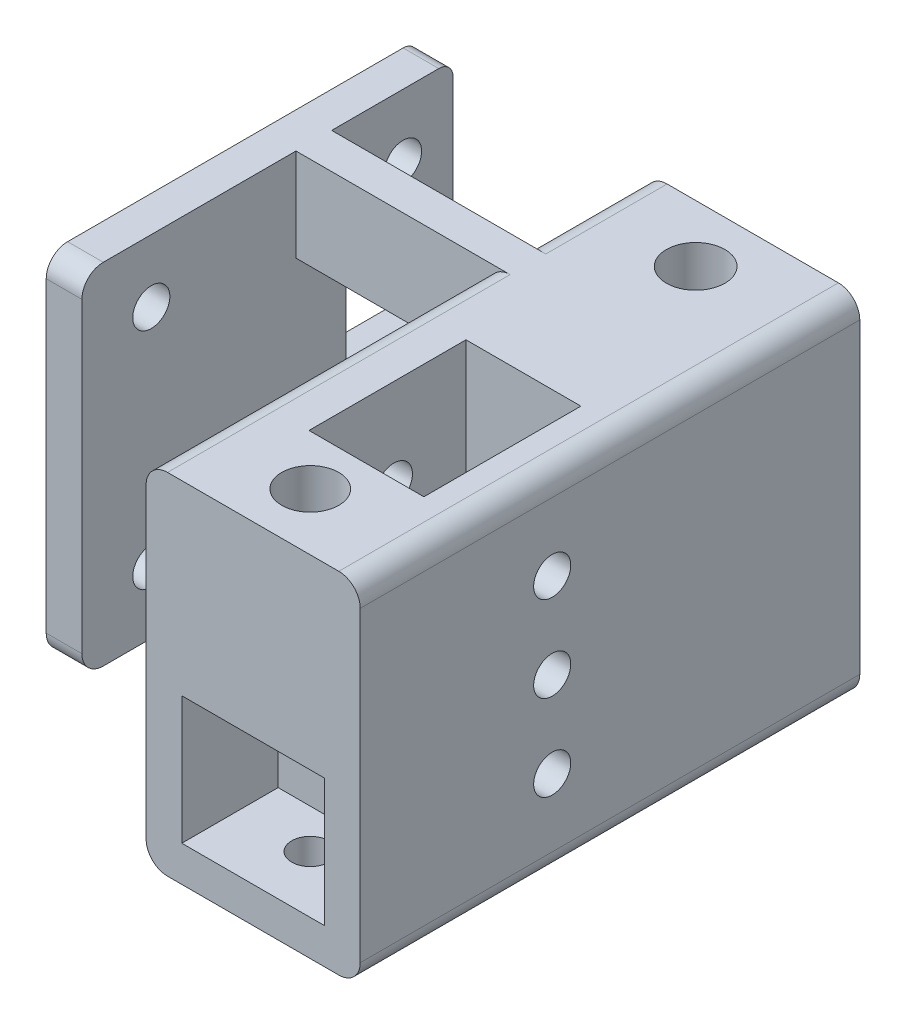
SolidWorks part; units mm, degrees
ref_plane "Front Plane" through (0, 0, 0) normal (0, 0, 1) x (1, 0, 0)
ref_plane "Top Plane" through (0, 0, 0) normal (0, 1, 0) x (1, 0, 0)
ref_plane "Right Plane" through (0, 0, 0) normal (1, 0, 0) x (0, 0, -1)
sketch "Sketch1" plane through (0, 0, 0) normal (0, 0, 1) x (1, 0, 0)
  circle A0 centre (0, 0) radius 11
  dimension "D1" = 22
extrude "Boss-Extrude1" add sketch "Sketch1" along normal blind 3
sketch "Sketch2" plane through (0, 0, 3) normal (0, 0, 1) x (1, 0, 0)
  circle A0 centre (0, 0) radius 5.25
  dimension "D1" = 10.5
extrude "Cut-Extrude1" cut sketch "Sketch2" against normal through all
sketch "Sketch3" plane through (0, 0, 3) normal (0, 0, 1) x (1, 0, 0)
  circle A0 centre (0, 8.5) radius 1.5
  circle A1 centre (-8.5, 0) radius 1.5
  circle A2 centre (0, -8.5) radius 1.5457
  circle A3 centre (8.5, 0) radius 1.5
  dimension "D1" = 3
  dimension "D2" = 3.0914
  dimension "D3" = 3
  dimension "D4" = 3
extrude "Cut-Extrude2" cut sketch "Sketch3" against normal through all
sketch "Sketch4" plane through (0, 0, 0) normal (0, 1, 0) x (1, 0, 0)
  line L1 (27.8591, -3) -> (0, -3)
  line L2 (27.8591, -3) -> (27.8591, -0.9879)
  line L3 (27.8591, -0.9879) -> (0, -0.9879)
  line L4 (0, -3) -> (0, -0.9879)
  dimension "D1" = 2.0121
extrude "Boss-Extrude3" add sketch "Sketch4" along normal mid plane 22
sketch "Sketch5" plane through (0, 0, 0.9879) normal (0, 0, -1) x (-1, 0, 0)
  circle A0 centre (0, 0) radius 5.25
extrude "Cut-Extrude3" cut sketch "Sketch5" against normal through all
sketch "Sketch6" plane through (0, 0, 0) normal (0, 0, -1) x (-1, 0, 0)
  line L0 (0, 10) -> (0, 7) construction
  line L1 (0, -6.9543) -> (0, -10.0457) construction
  circle A0 centre (-8.5, 0) radius 1.5
  circle A1 centre (0, 8.5) radius 1.5
  circle A2 centre (0, -8.5) radius 1.5457
extrude "Cut-Extrude4" cut sketch "Sketch6" against normal through all
sketch "Sketch7" plane through (0, 0, 0.9879) normal (0, 0, -1) x (-1, 0, 0)
  line L0 (-11, 0) -> (-24, 0)
  line L1 (-27.8591, -11) -> (0, -11) construction
  line L2 (-27.8591, 11) -> (-24, 11)
  line L3 (-27.8591, 11) -> (-27.8591, -11)
  line L4 (-27.8591, -11) -> (-24, -11)
  line L5 (-24, 11) -> (-24, -11)
  arc A0 (0, 11) -> (0, -11) centre (0, 0) ccw construction
  line M6 (-27.8591, -11) -> (0, -11)
  line M8 (0, 11) -> (-27.8591, 11)
  line M9 (-27.8591, 11) -> (-27.8591, -11)
  dimension "D1" = 13
extrude "Cut-Extrude5" cut sketch "Sketch7" against normal blind 10 contours L5 M8 M9 M6 region at (25.9295, 0, 0.9879)
sketch "Sketch10" plane through (0, 0, 3) normal (0, 0, 1) x (1, 0, 0)
  line L1 (0, 11) -> (24, 11)
  line L2 (0, 11) -> (0, -11)
  line L3 (0, -11) -> (24, -11)
  line L4 (24, 11) -> (24, -11)
  circle A0 centre (0, 0) radius 11
  circle M1 centre (8.5, 0) radius 1.5
  circle M2 centre (0, 8.5) radius 1.5
  circle M3 centre (0, -8.5) radius 1.5457
  circle M4 centre (0, 0) radius 5.25
  circle M5 centre (-8.5, 0) radius 1.5
  line M6 (0, -11) -> (24, -11)
  line M7 (24, -11) -> (24, 11)
  line M8 (24, 11) -> (0, 11)
  arc M9 (0, 11) -> (0, -11) centre (0, 0) ccw
extrude "Boss-Extrude5" add sketch "Sketch10" along normal blind 5 contours A0 M6 M7 M8 | L2 A0 M2 M4 M3 M1 | L2 M9 M3 M4 M2 M5 region at (5.4833, 0.014, 3) region at (16.1235, 0, 3) region at (-5.4833, 0.014, 3)
sketch "Sketch11" plane through (0, -11, 0) normal (0, -1, 0) x (1, 0, 0)
  line L0 (24, 0.9879) -> (0, 0.9879) construction
  line L1 (24, 8) -> (6, 8)
  line L2 (24, 8) -> (24, 0.9879)
  line L3 (24, 0.9879) -> (6, 0.9879)
  line L4 (6, 8) -> (6, 0.9879)
  dimension "D1" = 18
extrude "Boss-Extrude7" add sketch "Sketch11" along normal blind 13
sketch "Sketch13" plane through (0, 0, 0.9879) normal (0, 0, -1) x (-1, 0, 0)
  line L0 (-6, -11) -> (-34.4381, -11) construction
  line L1 (-24, 11) -> (-24, -24) construction
  line L2 (-24, -14.5) -> (-18, -14.5)
  line L3 (-24, -14.5) -> (-24, -22.5)
  line L4 (-24, -22.5) -> (-18, -22.5)
  line L5 (-18, -14.5) -> (-18, -22.5)
  dimension "D1" = 0
  dimension "D2" = 8
  dimension "D3" = 3.5
  dimension "D4" = 6
extrude "Boss-Extrude8" add sketch "Sketch13" along normal blind 10
sketch "Sketch14" plane through (0, 0, 0.9879) normal (0, 0, -1) x (-1, 0, 0)
  line L1 (-6, -24) -> (-24, -24)
  line L2 (-6, -24) -> (-6, -22.5)
  line L3 (-6, -22.5) -> (-24, -22.5)
  line L4 (-24, -24) -> (-24, -22.5)
extrude "Cut-Extrude6" cut sketch "Sketch14" against normal blind 10
sketch "Sketch15" plane through (0, 0, 8) normal (0, 0, 1) x (1, 0, 0)
  line L0 (6, -11) -> (35.8842, -11) construction
  line L1 (24, -22.5) -> (16, -22.5)
  line L2 (24, -22.5) -> (24, -14.5)
  line L3 (24, -14.5) -> (16, -14.5)
  line L4 (16, -22.5) -> (16, -14.5)
  dimension "D1" = 3.5
  dimension "D2" = 8
extrude "Boss-Extrude9" add sketch "Sketch15" along normal blind 30
sketch "Sketch16" plane through (0, 0, 0.9879) normal (0, 0, -1) x (-1, 0, 0)
  line L0 (-24, -14.5) -> (5.1357, -14.5) construction
  line L2 (-18, -22.5) -> (-16, -22.5)
  line L3 (-18, -22.5) -> (-18, -14.5)
  line L4 (-18, -14.5) -> (-16, -14.5)
  line L5 (-16, -22.5) -> (-16, -14.5)
  dimension "D1" = 2
extrude "Boss-Extrude10" add sketch "Sketch16" along normal blind 10
sketch "Sketch18" plane through (24, 0, 0) normal (1, 0, 0) x (0, 0, -1)
  line L1 (-38, -14.5) -> (9.0121, -14.5)
  line L2 (-38, -14.5) -> (-38, -11)
  line L3 (-38, -11) -> (9.0121, -11)
  line L4 (9.0121, -14.5) -> (9.0121, -11)
  dimension "D1" = 3.5
extrude "Boss-Extrude11" add sketch "Sketch18" against normal blind 8
sketch "Sketch19" plane through (24, 0, 0) normal (1, 0, 0) x (0, 0, -1)
  line L1 (-38, -11) -> (9.0121, -11)
  line L2 (-38, -11) -> (-38, -6)
  line L3 (-38, -6) -> (9.0121, -6)
  line L4 (9.0121, -11) -> (9.0121, -6)
  dimension "D1" = 5
extrude "Boss-Extrude12" add sketch "Sketch19" against normal blind 8
sketch "Sketch20" plane through (24, 0, 0) normal (1, 0, 0) x (0, 0, -1)
  line L0 (9.0121, -6) -> (9.0121, -11) construction
  line L1 (9.0121, -6) -> (9.0121, -22.5) construction
  line L2 (9.0121, -11) -> (-47.1773, -11) construction
  line L3 (9.0121, -11) -> (9.0121, -14.5) construction
  line L4 (9.0121, -14.5) -> (-46.6015, -14.5) construction
  line L5 (9.0121, -14.5) -> (9.0121, -19.5) construction
  line L6 (9.0121, -17) -> (-43.5925, -17) construction
  circle A0 centre (2.7978, -17) radius 2.75
  dimension "D4" = 5.5
  dimension "D1" = 5
  dimension "D2" = 3.5
  dimension "D3" = 5
extrude "Cut-Extrude7" cut sketch "Sketch20" against normal blind 8
sketch "Sketch21" plane through (24, 0, 0) normal (1, 0, 0) x (0, 0, -1)
  line L1 (-38, -22.5) -> (-8, -22.5)
  line L2 (-38, -22.5) -> (-38, -6)
  line L3 (-38, -6) -> (-8, -6)
  line L4 (-8, -22.5) -> (-8, -6)
extrude "Cut-Extrude8" cut sketch "Sketch21" against normal blind 8
sketch "Sketch22" plane through (0, -22.5, 0) normal (0, -1, 0) x (1, 0, 0)
  line L0 (6, 8) -> (24, 8)
  line L1 (24, 8) -> (24, -9.0121)
  line L2 (24, -9.0121) -> (16, -9.0121)
  line L3 (16, -9.0121) -> (16, 0.9879)
  line L4 (16, 0.9879) -> (6, 0.9879)
  line L5 (6, 0.9879) -> (6, 8)
extrude "Boss-Extrude13" add sketch "Sketch22" along normal blind 2
fillet "Fillet4" radius 2 2 edges at (20, -6, -9.0121) (20, -24.5, -9.0121)
sketch "Sketch24" plane through (0, 11, 0) normal (0, 1, 0) x (1, 0, 0)
  line L0 (24, -8) -> (0, -8) construction
  line L1 (24, -0.9879) -> (6, -0.9879)
  line L2 (24, -0.9879) -> (24, -8)
  line L3 (24, -8) -> (6, -8)
  line L4 (6, -0.9879) -> (6, -8)
  dimension "D1" = 18
extrude "Boss-Extrude14" add sketch "Sketch24" along normal blind 13.5
sketch "Sketch25" plane through (24, 0, 0) normal (1, 0, 0) x (0, 0, -1)
  line L1 (-0.9879, 24.5) -> (9.2401, 24.5)
  line L2 (-0.9879, 24.5) -> (-0.9879, 6)
  line L3 (-0.9879, 6) -> (9.2401, 6)
  line L4 (9.2401, 24.5) -> (9.2401, 6)
  dimension "D1" = 18.5
extrude "Boss-Extrude15" add sketch "Sketch25" against normal blind 8
sketch "Sketch26" plane through (24, 0, 0) normal (1, 0, 0) x (0, 0, -1)
  line L0 (9.2401, 6) -> (9.2401, 11) construction
  line L1 (9.2401, 6) -> (9.2401, 24.5) construction
  line L2 (9.2401, 11) -> (-25.444, 11) construction
  line L3 (9.2401, 11) -> (9.2401, 14.5) construction
  line L4 (9.2401, 14.5) -> (-21.9918, 14.5) construction
  line L5 (9.2401, 14.5) -> (9.2401, 19.5) construction
  line L6 (2.7978, -17) -> (2.7978, 39.4291) construction
  circle A0 centre (2.7978, 17) radius 2.6
  dimension "D4" = 5.2
  dimension "D1" = 5
  dimension "D2" = 3.5
  dimension "D3" = 5
extrude "Cut-Extrude9" cut sketch "Sketch26" against normal blind 8
fillet "Fillet6" radius 2 2 edges at (20, 24.5, -9.2401) (20, 6, -9.2401)
sketch "Sketch27" plane through (24, 0, 0) normal (1, 0, 0) x (0, 0, -1)
  line L1 (-1.9691, 21.4381) -> (6.5233, 21.4381)
  line L2 (-1.9691, 21.4381) -> (-1.9691, 12.6005)
  line L3 (-1.9691, 12.6005) -> (6.5233, 12.6005)
  line L4 (6.5233, 21.4381) -> (6.5233, 12.6005)
extrude "Boss-Extrude16" add sketch "Sketch27" against normal blind 8
sketch "Sketch28" plane through (24, 0, 0) normal (1, 0, 0) x (0, 0, -1)
  line L0 (-0.9879, -6) -> (-0.9879, -11) construction
  line L2 (-2.5214, -12.8767) -> (6.8685, -12.8767)
  line L3 (-2.5214, -12.8767) -> (-2.5214, -20.1263)
  line L4 (-2.5214, -20.1263) -> (6.8685, -20.1263)
  line L5 (6.8685, -12.8767) -> (6.8685, -20.1263)
extrude "Boss-Extrude17" add sketch "Sketch28" against normal blind 8
sketch "Sketch30" plane through (0, 0, -9.2401) normal (0, 0, -1) x (-1, 0, 0)
  line L1 (-24, 22.5) -> (-16, 22.5)
  line L2 (-24, 22.5) -> (-24, 24.5)
  line L3 (-24, 24.5) -> (-16, 24.5)
  line L4 (-16, 22.5) -> (-16, 24.5)
  line L5 (-24, 8) -> (-16, 8)
  line L6 (-24, 8) -> (-24, 6)
  line L7 (-24, 6) -> (-16, 6)
  line L8 (-16, 8) -> (-16, 6)
extrude "Boss-Extrude19" add sketch "Sketch30" against normal blind 8
sketch "Sketch31" plane through (0, 0, -9.0121) normal (0, 0, -1) x (-1, 0, 0)
  line L1 (-24, -8) -> (-16, -8)
  line L2 (-24, -8) -> (-24, -6)
  line L3 (-24, -6) -> (-16, -6)
  line L4 (-16, -8) -> (-16, -6)
  line L5 (-24, -22.5) -> (-16, -22.5)
  line L6 (-24, -22.5) -> (-24, -24.5)
  line L7 (-24, -24.5) -> (-16, -24.5)
  line L8 (-16, -22.5) -> (-16, -24.5)
extrude "Boss-Extrude20" add sketch "Sketch31" against normal blind 8
sketch "Sketch32" plane through (0, 0, -9.2401) normal (0, 0, -1) x (-1, 0, 0)
  line L1 (-24, 24.5) -> (-16, 24.5)
  line L2 (-24, 24.5) -> (-24, 6)
  line L3 (-24, 6) -> (-16, 6)
  line L4 (-16, 24.5) -> (-16, 6)
extrude "Boss-Extrude22" add sketch "Sketch32" along normal blind 5
sketch "Sketch33" plane through (0, 0, -9.0121) normal (0, 0, -1) x (-1, 0, 0)
  line L1 (-24, -6) -> (-16, -6)
  line L2 (-24, -6) -> (-24, -24.5)
  line L3 (-24, -24.5) -> (-16, -24.5)
  line L4 (-16, -6) -> (-16, -24.5)
extrude "Boss-Extrude23" add sketch "Sketch33" along normal blind 5
sketch "Sketch34" plane through (24, 0, 0) normal (1, 0, 0) x (0, 0, -1)
  line L0 (-0.9879, -11) -> (-0.9879, 11) construction
  line L1 (-0.9879, -6) -> (-0.9879, -11) construction
  line L3 (-0.9879, -11) -> (-0.9879, -14.2) construction
  line L5 (-0.9879, -14.2) -> (-0.9879, -19.2) construction
  line L9 (6.5121, -6) -> (6.5121, -24.5) construction
  line L10 (14.0121, -6) -> (-0.9879, -6) construction
  line L11 (14.0121, -24.5) -> (-8, -24.5) construction
  circle A0 centre (6.0121, 16.7) radius 2.6
  dimension "D8" = 5.2
  dimension "D1" = 7
  dimension "D2" = 5
  dimension "D4" = 3.2
  dimension "D6" = 5
extrude "Cut-Extrude11" cut sketch "Sketch34" against normal through all
sketch "Sketch35" plane through (24, 0, 0) normal (1, 0, 0) x (0, 0, -1)
  line L0 (14.0121, -6) -> (-0.9879, -6) construction
  circle A0 centre (6.0121, -16.7) radius 2.6
  dimension "D1" = 5.2
  dimension "D2" = 10.7
extrude "Cut-Extrude12" cut sketch "Sketch35" against normal through all
sketch "Sketch36" plane through (0, -24.5, 0) normal (0, -1, 0) x (1, 0, 0)
  line L1 (16, -14.2401) -> (24, -14.2401)
  line L2 (16, -14.2401) -> (16, -14.0121)
  line L3 (16, -14.0121) -> (24, -14.0121)
  line L4 (24, -14.2401) -> (24, -14.0121)
extrude "Cut-Extrude13" cut sketch "Sketch36" against normal through all
sketch "Sketch37" plane through (0, 0, -14.0121) normal (0, 0, -1) x (-1, 0, 0)
  line L0 (-24, -24.5) -> (-16, -24.5) construction
  line L1 (-16, -6) -> (-19, -6)
  line L2 (-16, -6) -> (-16, -24.5)
  line L3 (-16, -24.5) -> (-19, -24.5)
  line L4 (-19, -6) -> (-19, -24.5)
  dimension "D1" = 3
extrude "Cut-Extrude14" cut sketch "Sketch37" against normal blind 15
sketch "Sketch38" plane through (0, 0, -14.0121) normal (0, 0, -1) x (-1, 0, 0)
  line L0 (-24, 6) -> (-16, 6) construction
  line L1 (-16, 24.5) -> (-19, 24.5)
  line L2 (-16, 24.5) -> (-16, 6)
  line L3 (-16, 6) -> (-19, 6)
  line L4 (-19, 24.5) -> (-19, 6)
  dimension "D1" = 3
extrude "Cut-Extrude15" cut sketch "Sketch38" against normal blind 15
fillet "Fillet9" radius 2 4 edges at (21.5, -24.5, -14.0121) (21.5, -6, -14.0121) (21.5, 24.5, -14.0121) (21.5, 6, -14.0121)
sketch "Sketch39" plane through (24, 0, 0) normal (1, 0, 0) x (0, 0, -1)
  line L1 (2.5573, 21.5762) -> (10.9806, 21.5762)
  line L2 (2.5573, 21.5762) -> (2.5573, 11.841)
  line L3 (2.5573, 11.841) -> (10.9806, 11.841)
  line L4 (10.9806, 21.5762) -> (10.9806, 11.841)
  line L5 (1.7978, -12.6696) -> (10.4283, -12.6696)
  line L6 (1.7978, -12.6696) -> (1.7978, -21.0239)
  line L7 (1.7978, -21.0239) -> (10.4283, -21.0239)
  line L8 (10.4283, -12.6696) -> (10.4283, -21.0239)
extrude "Boss-Extrude24" add sketch "Sketch39" against normal blind 8
sketch "Sketch40" plane through (24, 0, 0) normal (1, 0, 0) x (0, 0, -1)
  line L0 (-0.9879, 6) -> (12.0121, 6) construction
  line L1 (-8, -24.5) -> (-8, 24.5) construction
  circle A0 centre (7, 15.7) radius 2.6
  dimension "D2" = 15
  dimension "D3" = 5.2
  dimension "D1" = 9.7
extrude "Cut-Extrude16" cut sketch "Sketch40" against normal blind 8
sketch "Sketch41" plane through (0, 0, -10.9806) normal (0, 0, -1) x (-1, 0, 0)
  line L1 (-16, 21.5762) -> (-19, 21.5762)
  line L2 (-16, 21.5762) -> (-16, 11.841)
  line L3 (-16, 11.841) -> (-19, 11.841)
  line L4 (-19, 21.5762) -> (-19, 11.841)
extrude "Cut-Extrude18" cut sketch "Sketch41" against normal blind 9
sketch "Sketch42" plane through (0, 0, -10.4283) normal (0, 0, -1) x (-1, 0, 0)
  line L1 (-19, -12.6696) -> (-16, -12.6696)
  line L2 (-19, -12.6696) -> (-19, -21.0239)
  line L3 (-19, -21.0239) -> (-16, -21.0239)
  line L4 (-16, -12.6696) -> (-16, -21.0239)
extrude "Cut-Extrude19" cut sketch "Sketch42" against normal blind 9
sketch "Sketch43" plane through (24, 0, 0) normal (1, 0, 0) x (0, 0, -1)
  line L0 (12.0121, -6) -> (-0.9879, -6) construction
  line L1 (-8, -24.5) -> (-8, 24.5) construction
  circle A0 centre (7, -15.7) radius 2.6
  dimension "D1" = 5.2
  dimension "D3" = 15
  dimension "D2" = 9.7
extrude "Cut-Extrude20" cut sketch "Sketch43" against normal blind 9
sketch "Sketch48" plane through (0, 0, 8) normal (0, 0, 1) x (1, 0, 0)
  line L1 (24, -24.5) -> (46, -24.5)
  line L2 (24, -24.5) -> (24, -11.5)
  line L3 (24, -11.5) -> (46, -11.5)
  line L4 (46, -24.5) -> (46, -11.5)
  dimension "D1" = 13
  dimension "D2" = 22
extrude "Boss-Extrude26" add sketch "Sketch48" against normal blind 5
sketch "Sketch49" plane through (0, 0, 8) normal (0, 0, 1) x (1, 0, 0)
  line L1 (24, 24.5) -> (46, 24.5)
  line L2 (24, 24.5) -> (24, 11.5)
  line L3 (24, 11.5) -> (46, 11.5)
  line L4 (46, 24.5) -> (46, 11.5)
  dimension "D1" = 22
  dimension "D2" = 13
extrude "Boss-Extrude27" add sketch "Sketch49" against normal blind 5
sketch "Sketch50" plane through (46, 0, 0) normal (1, 0, 0) x (0, 0, -1)
  line L1 (-8, 24.5) -> (-3, 24.5)
  line L2 (-8, 24.5) -> (-8, -24.5)
  line L3 (-8, -24.5) -> (-3, -24.5)
  line L4 (-3, 24.5) -> (-3, -24.5)
extrude "Boss-Extrude28" add sketch "Sketch50" along normal blind 15
sketch "Sketch51" plane through (0, 0, 8) normal (0, 0, 1) x (1, 0, 0)
  line L0 (61, 24.5) -> (61, -24.5) construction
  line L1 (6, 24.5) -> (61, 24.5)
  line L2 (6, 24.5) -> (6, 19.5)
  line L3 (6, 19.5) -> (61, 19.5)
  line L4 (61, 24.5) -> (61, 19.5)
  dimension "D1" = 5
extrude "Boss-Extrude29" add sketch "Sketch51" along normal blind 42.8
sketch "Sketch52" plane through (0, 19.5, 0) normal (0, -1, 0) x (1, 0, 0)
  line L1 (6, 50.8) -> (61, 50.8)
  line L2 (6, 50.8) -> (6, 55.8)
  line L3 (6, 55.8) -> (61, 55.8)
  line L4 (61, 50.8) -> (61, 55.8)
  dimension "D1" = 5
extrude "Boss-Extrude30" add sketch "Sketch52" against normal blind 47.8
sketch "Sketch53" plane through (0, 0, 55.8) normal (0, 0, 1) x (1, 0, 0)
  line L1 (6, 67.3) -> (61, 67.3)
  line L2 (6, 67.3) -> (6, 72.3)
  line L3 (6, 72.3) -> (61, 72.3)
  line L4 (61, 67.3) -> (61, 72.3)
  dimension "D1" = 5
extrude "Boss-Extrude31" add sketch "Sketch53" against normal blind 47.8
sketch "Sketch55" plane through (0, 72.3, 0) normal (0, 1, 0) x (1, 0, 0)
  line L0 (61, -55.8) -> (6, -55.8) construction
  line L1 (61, -8) -> (46, -8)
  line L2 (61, -8) -> (61, -55.8)
  line L3 (61, -55.8) -> (46, -55.8)
  line L4 (46, -8) -> (46, -55.8)
  dimension "D1" = 15
extrude "Cut-Extrude21" cut sketch "Sketch55" against normal through all
sketch "Sketch57" plane through (46, 0, 0) normal (1, 0, 0) x (0, 0, -1)
  line L1 (-8, 72.3) -> (-55.8, 72.3)
  line L2 (-8, 72.3) -> (-8, 19.5)
  line L3 (-8, 19.5) -> (-55.8, 19.5)
  line L4 (-55.8, 72.3) -> (-55.8, 19.5)
extrude "Boss-Extrude32" add sketch "Sketch57" along normal blind 5
sketch "Sketch58" plane through (51, 0, 0) normal (1, 0, 0) x (0, 0, -1)
  circle A0 centre (-29.4, 45.9) radius 11.5
  dimension "D1" = 23
extrude "Cut-Extrude25" cut sketch "Sketch58" against normal through all
sketch "Sketch61" plane through (0, 72.3, 0) normal (0, 1, 0) x (1, 0, 0)
  line L0 (51, -8) -> (6, -8) construction
  line L1 (16, -45.8) -> (41, -45.8)
  line L2 (16, -45.8) -> (16, -18)
  line L3 (16, -18) -> (41, -18)
  line L4 (41, -45.8) -> (41, -18)
  line L5 (16, -45.8) -> (41, -18) construction
  line L6 (16, -18) -> (41, -45.8) construction
  line L7 (51, -55.8) -> (6, -55.8) construction
  line L8 (6, -8) -> (6, -55.8) construction
  line L9 (51, -8) -> (51, -55.8) construction
  point P0 (28.5, -31.9)
  dimension "D1" = 10
  dimension "D2" = 10
  dimension "D3" = 10
  dimension "D4" = 10
extrude "Cut-Extrude26" cut sketch "Sketch61" against normal through all
sketch "Sketch62" plane through (46, 0, 0) normal (-1, 0, 0) x (0, 0, 1)
  line L0 (50.8, 24.5) -> (8, 24.5) construction
  line L1 (50.8, 24.5) -> (50.8, 67.3) construction
  circle A0 centre (46.3, 29) radius 1.75
  dimension "D1" = 3.5
  dimension "D3" = 4.5
  dimension "D2" = 4.5
extrude "Cut-Extrude28" cut sketch "Sketch62" against normal through all
sketch "Sketch63" plane through (46, 0, 0) normal (-1, 0, 0) x (0, 0, 1)
  line L0 (8, 24.5) -> (8, 67.3) construction
  line L1 (50.8, 24.5) -> (8, 24.5) construction
  circle A0 centre (12.5, 29) radius 1.75
  dimension "D1" = 3.5
  dimension "D2" = 4.5
  dimension "D3" = 4.5
extrude "Cut-Extrude29" cut sketch "Sketch63" against normal through all
sketch "Sketch64" plane through (46, 0, 0) normal (-1, 0, 0) x (0, 0, 1)
  line L0 (50.8, 67.3) -> (8, 67.3) construction
  line L1 (50.8, 67.3) -> (50.8, 24.5) construction
  circle A0 centre (46.3, 62.8) radius 1.75
  dimension "D1" = 3.5
  dimension "D2" = 4.5
  dimension "D3" = 4.5
extrude "Cut-Extrude30" cut sketch "Sketch64" against normal through all
sketch "Sketch65" plane through (46, 0, 0) normal (-1, 0, 0) x (0, 0, 1)
  line L0 (8, 24.5) -> (8, 67.3) construction
  line L1 (50.8, 67.3) -> (8, 67.3) construction
  circle A0 centre (12.5, 62.8) radius 1.75
  dimension "D1" = 4.5
  dimension "D2" = 3.5
  dimension "D3" = 4.5
extrude "Cut-Extrude31" cut sketch "Sketch65" against normal through all
sketch "Sketch67" plane through (61, 0, 0) normal (1, 0, 0) x (0, 0, -1)
  line L1 (-8, 24.5) -> (-3, 24.5)
  line L2 (-8, 24.5) -> (-8, -24.5)
  line L3 (-8, -24.5) -> (-3, -24.5)
  line L4 (-3, 24.5) -> (-3, -24.5)
extrude "Boss-Extrude33" add sketch "Sketch67" along normal blind 5
sketch "Sketch68" plane through (0, -24.5, 0) normal (0, -1, 0) x (1, 0, 0)
  line L1 (66, 3) -> (51, 3)
  line L2 (66, 3) -> (66, -14.0121)
  line L3 (66, -14.0121) -> (51, -14.0121)
  line L4 (51, 3) -> (51, -14.0121)
  line L5 (66, 8) -> (51, 8)
  line L6 (66, 8) -> (66, 55.8)
  line L7 (66, 55.8) -> (51, 55.8)
  line L8 (51, 8) -> (51, 55.8)
extrude "Boss-Extrude34" add sketch "Sketch68" against normal blind 15
sketch "Sketch69" plane through (66, 0, 0) normal (1, 0, 0) x (0, 0, -1)
  line L0 (-55.8, -9.5) -> (-8, -9.5)
  line L1 (-8, -9.5) -> (-8, 24.5)
  line L2 (-8, 24.5) -> (-3, 24.5)
  line L3 (-3, 24.5) -> (-3, -9.5)
  line L4 (-3, -9.5) -> (14.0121, -9.5)
  line L5 (14.0121, -9.5) -> (14.0121, -24.5)
  line L6 (14.0121, -24.5) -> (-55.8, -24.5)
  line L7 (-55.8, -24.5) -> (-55.8, -9.5)
extrude "Boss-Extrude36" add sketch "Sketch69" along normal blind 15
sketch "Sketch70" plane through (0, -24.5, 0) normal (0, -1, 0) x (1, 0, 0)
  line L0 (81, 55.8) -> (51, 55.8) construction
  line L1 (51, -14.0121) -> (81, -14.0121) construction
  circle A0 centre (66, 47.8) radius 4.1
  circle A1 centre (66, -6.0121) radius 4.1
  dimension "D1" = 8
  dimension "D2" = 8.2
  dimension "D3" = 8.2
  dimension "D4" = 8
extrude "Cut-Extrude32" cut sketch "Sketch70" against normal blind 10
sketch "Sketch72" plane through (0, -24.5, 0) normal (0, -1, 0) x (1, 0, 0)
  line L1 (57, 40) -> (75, 40)
  line L2 (57, 40) -> (57, 18)
  line L3 (57, 18) -> (75, 18)
  line L4 (75, 40) -> (75, 18)
  line L5 (6, 8) -> (51, 8) construction
  line L6 (51, 55.8) -> (51, 8) construction
  line L9 (81, 55.8) -> (81, -14.0121) construction
  dimension "D1" = 6
  dimension "D2" = 10
  dimension "D3" = 22
  dimension "D4" = 6
extrude "Cut-Extrude33" cut sketch "Sketch72" against normal through all
fillet "Fillet10" radius 4 1 edges at (81, 24.5, 5.5)
fillet "Fillet12" radius 4 1 edges at (6, -24.5, 4.494)
fillet "Fillet13" radius 4 9 edges at (51, -17, -14.0121) (81, -9.5, -5.506) (81, -17, -14.0121) (81, -24.5, 20.894) (81, -9.5, 31.9) (51, -9.5, 31.9) (51, -9.5, -5.506) (51, -24.5, -5.506) (51, -24.5, 31.9)
sketch "Sketch77" plane through (0, 0, 0.9879) normal (0, 0, -1) x (-1, 0, 0)
  line L1 (-19, 24.5) -> (17.4446, 24.5)
  line L2 (-19, 24.5) -> (-19, -26.3623)
  line L3 (-19, -26.3623) -> (17.4446, -26.3623)
  line L4 (17.4446, 24.5) -> (17.4446, -26.3623)
extrude "Cut-Extrude38" cut sketch "Sketch77" against normal through all
sketch "Sketch78" plane through (0, 0, 8) normal (0, 0, -1) x (-1, 0, 0)
  line L1 (-51, 72.3) -> (-6, 72.3)
  line L2 (-51, 72.3) -> (-51, 24.5)
  line L3 (-51, 24.5) -> (-6, 24.5)
  line L4 (-6, 72.3) -> (-6, 24.5)
extrude "Cut-Extrude39" cut sketch "Sketch78" against normal through all
sketch "Sketch79" plane through (0, -24.5, 0) normal (0, -1, 0) x (1, 0, 0)
  line L1 (51, 3) -> (82.4311, 3)
  line L2 (51, 3) -> (51, -15.5183)
  line L3 (51, -15.5183) -> (82.4311, -15.5183)
  line L4 (82.4311, 3) -> (82.4311, -15.5183)
extrude "Cut-Extrude40" cut sketch "Sketch79" against normal through all
sketch "Sketch80" plane through (0, 24.5, 0) normal (0, 1, 0) x (1, 0, 0)
  line L0 (19, -55.8) -> (19, -45.8) construction
  line L1 (81, -8) -> (19, -8)
  line L2 (81, -8) -> (81, -55.8)
  line L3 (81, -55.8) -> (19, -55.8)
  line L4 (19, -8) -> (19, -55.8)
  line L5 (51, -55.8) -> (19, -55.8) construction
extrude "Cut-Extrude41" cut sketch "Sketch80" against normal through all
sketch "Sketch81" plane through (0, 0, 0) normal (0, 0, -1) x (-1, 0, 0)
  circle A0 centre (0, 0) radius 11
extrude "Cut-Extrude42" cut sketch "Sketch81" against normal through all
sketch "Sketch85" plane through (0, 0, 3) normal (0, 0, -1) x (-1, 0, 0)
  line L0 (-24, -24.5) -> (-77, -24.5) construction
  line L1 (-81, 24.5) -> (-51, 24.5)
  line L2 (-81, 24.5) -> (-81, -24.5)
  line L3 (-81, -24.5) -> (-51, -24.5)
  line L4 (-51, 24.5) -> (-51, -24.5)
  dimension "D1" = 30
extrude "Boss-Extrude37" add sketch "Sketch85" along normal blind 17
sketch "Sketch86" plane through (0, 0, -14) normal (0, 0, -1) x (-1, 0, 0)
  line L1 (-81, 24.5) -> (-51, 24.5)
  line L2 (-81, 24.5) -> (-81, -24.5)
  line L3 (-81, -24.5) -> (-51, -24.5)
  line L4 (-51, 24.5) -> (-51, -24.5)
extrude "Boss-Extrude39" add sketch "Sketch86" against normal blind 70
sketch "Sketch87" plane through (0, 24.5, 0) normal (0, 1, 0) x (1, 0, 0)
  line L0 (51, 14) -> (81, 14) construction
  line L1 (51, -56) -> (81, -56) construction
  line L3 (58.8194, -19) -> (74.9193, -19)
  line L4 (58.8194, -19) -> (58.8194, -41)
  line L5 (58.8194, -41) -> (74.9193, -41)
  line L6 (74.9193, -19) -> (74.9193, -41)
  circle A0 centre (66, 6) radius 4.1
  circle A1 centre (66, -48) radius 4
  dimension "D1" = 8.2
  dimension "D3" = 8
  dimension "D2" = 8
  dimension "D4" = 8
  dimension "D5" = 15
  dimension "D6" = 22
extrude "Cut-Extrude43" cut sketch "Sketch87" against normal blind 70
fillet "Fillet17" radius 3 5 edges at (51, -24.5, 32) (81, -24.5, 21) (81, 24.5, 21) (51, 24.5, 32) (51, 24.5, -5.5)
sketch "Sketch89" plane through (0, 0, 8) normal (0, 0, 1) x (1, 0, 0)
  line L1 (19, 24.5) -> (24, 24.5)
  line L2 (19, 24.5) -> (19, -24.5)
  line L3 (19, -24.5) -> (24, -24.5)
  line L4 (24, 24.5) -> (24, -24.5)
extrude "Boss-Extrude40" add sketch "Sketch89" along normal blind 30
sketch "Sketch92" plane through (19, 0, 0) normal (-1, 0, 0) x (0, 0, 1)
  circle A0 centre (28.274, 15.7) radius 2.6
  circle A1 centre (28.274, -15.7) radius 2.6
  dimension "D1" = 5.2
  dimension "D2" = 5.2
extrude "Cut-Extrude44" cut sketch "Sketch92" against normal blind 10
fillet "Fillet18" radius 3 2 edges at (21.5, -24.5, 38) (21.5, 24.5, 38)
sketch "Sketch93" plane through (0, 0, -14) normal (0, 0, -1) x (-1, 0, 0)
  line L0 (-81, 21.5) -> (-81, -21.5) construction
  line L1 (-76, -19.5) -> (-56, -19.5)
  line L2 (-76, -19.5) -> (-76, -1.5535)
  line L3 (-76, -1.5535) -> (-56, -1.5535)
  line L4 (-56, -19.5) -> (-56, -1.5535)
  line L5 (-51, -24.5) -> (-51, 21.5) construction
  line L6 (-78, -24.5) -> (-51, -24.5) construction
  dimension "D1" = 5
  dimension "D2" = 5
  dimension "D3" = 5
extrude "Cut-Extrude45" cut sketch "Sketch93" against normal blind 17.8
sketch "Sketch98" plane through (81, 0, 0) normal (1, 0, 0) x (0, 0, -1)
  line L0 (14, 21.5) -> (14, -21.5) construction
  circle A0 centre (-29.1, 0) radius 2.6
  dimension "D1" = 5.2
  dimension "D2" = 43.1
extrude "Cut-Extrude46" cut sketch "Sketch98" against normal blind 37.8
sketch "Sketch99" plane through (81, 0, 0) normal (1, 0, 0) x (0, 0, -1)
  circle A0 centre (-29.1, 12) radius 2.6
  circle A1 centre (-29.1, 0) radius 2.6 construction
  dimension "D1" = 5.2
  dimension "D2" = 12
extrude "Cut-Extrude48" cut sketch "Sketch99" against normal blind 37.8
sketch "Sketch100" plane through (81, 0, 0) normal (1, 0, 0) x (0, 0, -1)
  circle A0 centre (-29.1, -12) radius 2.6
  circle A1 centre (-29.1, 0) radius 2.6 construction
  dimension "D1" = 5.2
  dimension "D2" = 12
extrude "Cut-Extrude49" cut sketch "Sketch100" against normal blind 37.8
sketch "Sketch102" plane through (0, 0, 56) normal (0, 0, 1) x (1, 0, 0)
  line L0 (78, -24.5) -> (54, -24.5) construction
  line L1 (56, -1.6) -> (76, -1.6)
  line L2 (56, -1.6) -> (56, -19.5)
  line L3 (56, -19.5) -> (76, -19.5)
  line L4 (76, -1.6) -> (76, -19.5)
  line L5 (81, 21.5) -> (81, -21.5) construction
  line L6 (51, -21.5) -> (51, 21.5) construction
  dimension "D1" = 5
  dimension "D2" = 5
  dimension "D3" = 5
  dimension "D4" = 17.9
extrude "Cut-Extrude50" cut sketch "Sketch102" against normal blind 13.5
sketch "Sketch103" plane through (0, -24.5, 0) normal (0, -1, 0) x (1, 0, 0)
  line L1 (60.309, 52.9076) -> (72.0485, 52.9076)
  line L2 (60.309, 52.9076) -> (60.309, 42.6479)
  line L3 (60.309, 42.6479) -> (72.0485, 42.6479)
  line L4 (72.0485, 52.9076) -> (72.0485, 42.6479)
extrude "Boss-Extrude41" add sketch "Sketch103" against normal blind 5
sketch "Sketch104" plane through (0, -24.5, 0) normal (0, -1, 0) x (1, 0, 0)
  line L1 (59.7171, -1.4492) -> (72.7391, -1.4492)
  line L2 (59.7171, -1.4492) -> (59.7171, -11.3143)
  line L3 (59.7171, -11.3143) -> (72.7391, -11.3143)
  line L4 (72.7391, -1.4492) -> (72.7391, -11.3143)
extrude "Boss-Extrude42" add sketch "Sketch104" against normal blind 5
sketch "Sketch105" plane through (0, -24.5, 0) normal (0, -1, 0) x (1, 0, 0)
  line L0 (78, -14) -> (51, -14) construction
  line L1 (78, 56) -> (54, 56) construction
  circle A0 centre (66, 48) radius 2.6
  circle A1 centre (66, -6) radius 2.6
  dimension "D1" = 5.2
  dimension "D2" = 5.2
  dimension "D4" = 8
  dimension "D3" = 8
extrude "Cut-Extrude51" cut sketch "Sketch105" against normal blind 15
